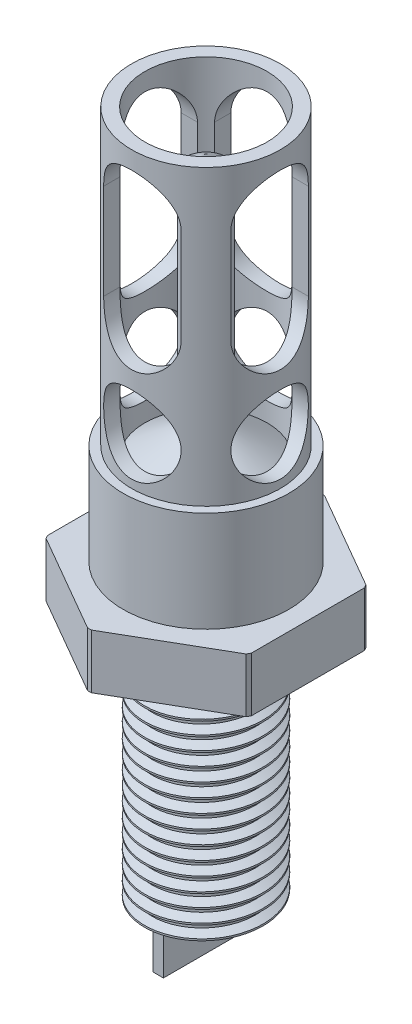
SolidWorks part; units mm, degrees
material "Brass UNS C36000 "
ref_plane "Front Plane" through (0, 0, 0) normal (0, 0, 1) x (1, 0, 0)
ref_plane "Top Plane" through (0, 0, 0) normal (0, 1, 0) x (1, 0, 0)
ref_plane "Right Plane" through (0, 0, 0) normal (1, 0, 0) x (0, 0, -1)
sketch "Sketch1" plane through (0, 0, 0) normal (0, 0, 1) x (1, 0, 0)
  line L0 (0, 0) -> (0, 144.5115) construction
  line L1 (0, 0) -> (5.5397, 0)
  line L2 (5.5397, 0) -> (5.5397, 18.923)
  line L3 (5.5397, 18.923) -> (4.7752, 18.923)
  line L4 (4.7752, 18.923) -> (4.7752, 22.098)
  line L5 (4.7752, 22.098) -> (6.35, 22.098)
  line L6 (6.35, 22.098) -> (6.35, 24.003)
  line L7 (6.35, 24.003) -> (8.5217, 24.003)
  line L8 (8.5217, 24.003) -> (8.5217, 22.098)
  line L9 (8.5217, 22.098) -> (10.8966, 22.098)
  line L10 (10.8966, 22.098) -> (10.8966, 27.178)
  line L11 (10.8966, 27.178) -> (7.747, 27.178)
  line L12 (7.747, 27.178) -> (7.747, 36.576)
  line L13 (7.747, 36.576) -> (6.9596, 36.576)
  line L14 (6.9596, 36.576) -> (6.9596, 64.008)
  line L15 (6.9596, 64.008) -> (5.715, 64.008)
  line L16 (5.715, 64.008) -> (5.715, 35.56)
  line L17 (5.715, 35.56) -> (1.8923, 37.973)
  line L18 (1.8923, 37.973) -> (1.8923, 59.0035)
  line L19 (1.8923, 59.0035) -> (0, 60.198)
  line L20 (0, 60.198) -> (0, 0)
  point P15 (0, 144.5115)
  point P23 (0, 0)
  point P24 (0, 0)
  point P25 (1.8812, 56.4758)
  point P26 (0, 113.7004)
  point P27 (4.7752, 15.9869)
  point P28 (10.0064, 41.8716)
  point P29 (0, 0)
  point P30 (7.747, 103.8076)
  point P31 (0, 0)
  point P32 (6.9596, 104.948)
  point P33 (1.8923, 38.9955)
  dimension "D1" = 11.0795
  dimension "D2" = 22.098
  dimension "D3" = 9.5504
  dimension "D4" = 3.175
  dimension "D5" = 12.7
  dimension "D6" = 17.0434
  dimension "D7" = 21.7932
  dimension "D8" = 1.905
  dimension "D9" = 15.494
  dimension "D10" = 13.9192
  dimension "D11" = 11.43
  dimension "D12" = 36.83
  dimension "D13" = 27.432
  dimension "D14" = 5.08
  dimension "D15" = 8.382
  dimension "D16" = 3.7846
  dimension "D17" = 33.02
  dimension "D18" = 22.225
revolve "Revolve1" add sketch "Sketch1" angle 360 about L0
ref_plane "Plane1" through (0, 0, -6.9596) normal (0, 0, -1) x (-1, 0, 0)
sketch "Sketch2" plane through (0, 0, -6.9596) normal (0, 0, 1) x (1, 0, 0)
  line L0 (0, 0) -> (0, 64.008) construction
  line L1 (5.715, 64.008) -> (-5.715, 64.008) construction
  line L2 (3.6195, 58.7375) -> (3.6195, 49.8221)
  line L3 (-3.6195, 58.7375) -> (-3.6195, 49.8221)
  arc A0 (3.6195, 58.7375) -> (-3.6195, 58.7375) centre (0, 58.7375) ccw
  arc A1 (-3.6195, 49.8221) -> (3.6195, 49.8221) centre (0, 49.8221) ccw
  circle A2 centre (0, 40.9575) radius 3.6195
  point P15 (0, 46.2026)
  point P16 (0, 62.357)
  point P17 (0, 44.577)
  dimension "D1" = 7.239
  dimension "D2" = 16.1544
  dimension "D3" = 1.651
  dimension "D4" = 1.6256
extrude "Cut-Extrude1" cut sketch "Sketch2" along normal blind 3.175
pattern_circular "CirPattern1" count 4 over 360 about axis through (0, 0, 0) along (0, -1, 0) of "Cut-Extrude1"
sketch "Sketch3" plane through (0, 27.178, 0) normal (0, 1, 0) x (1, 0, 0)
  line L1 (9.525, 5.4993) -> (0, 10.9985)
  line L2 (0, 10.9985) -> (-9.525, 5.4993)
  line L3 (-9.525, 5.4993) -> (-9.525, -5.4993)
  line L4 (-9.525, -5.4993) -> (0, -10.9985)
  line L5 (0, -10.9985) -> (9.525, -5.4993)
  line L6 (9.525, -5.4993) -> (9.525, 5.4993)
  circle A0 centre (0, 0) radius 9.525 construction
  circle A1 centre (0, 0) radius 12.7
  dimension "D1" = 19.05
  dimension "D2" = 25.4
extrude "Cut-Extrude2" cut sketch "Sketch3" against normal through all
ref_plane "Plane2" through (0, -2.54, 0) normal (0, -1, 0) x (-1, 0, 0)
sketch "Sketch4" plane through (0, -2.54, 0) normal (0, -1, 0) x (-1, 0, 0)
  circle A0 centre (0, 0) radius 5.127
  point P2 (0, 0)
  dimension "D1" = 10.254
curve "Helix/Spiral1" pitch 1.27 height 23.1775 radius 5.127 centre (0, -2.54, 0) axis (0, 1, 0) start towards (1, 0, 0)
sketch "Sketch5" plane through (0, 0, 0) normal (0, 0, 1) x (1, 0, 0)
  line L0 (4.5771, -2.54) -> (5.6769, -1.905) construction
  line L1 (5.6769, -1.905) -> (5.6769, -3.175)
  line L2 (5.6769, -3.175) -> (4.5771, -2.54) construction
  line L3 (4.5771, -2.54) -> (5.6769, -2.54) construction
  line L4 (-5.127, -2.54) -> (5.127, -2.54) construction
  line L5 (4.852, -2.3813) -> (4.852, -2.6987)
  line L6 (4.852, -2.3813) -> (5.6769, -1.905)
  line L7 (5.6769, -3.175) -> (4.852, -2.6987)
  point P4 (5.127, -2.54)
  dimension "D1" = 60
  dimension "D2" = 1.0998
  dimension "D3" = 0.275
sweep "Cut-Sweep1" cut profiles "Sketch5" path "Helix/Spiral1" align with end faces yes
sketch "Sketch6" plane through (0, 0, 0) normal (0, -1, 0) x (1, 0, 0)
  line L0 (0, 0) -> (-1.378, 0) construction
  line L1 (-1.378, 3.5941) -> (-0.3874, 3.5941)
  line L2 (-1.378, 3.5941) -> (-1.378, -3.5941)
  line L3 (-1.378, -3.5941) -> (-0.3874, -3.5941)
  line L4 (-0.3874, 3.5941) -> (-0.3874, -3.5941)
  circle A0 centre (0, 0) radius 5.5562 construction
  point P8 (5.5562, 0)
  dimension "D3" = 11.1125
  dimension "D1" = 7.1882
  dimension "D2" = 0.9906
  dimension "D4" = 5.9436
extrude "Boss-Extrude1" add sketch "Sketch6" along normal blind 4.9276
